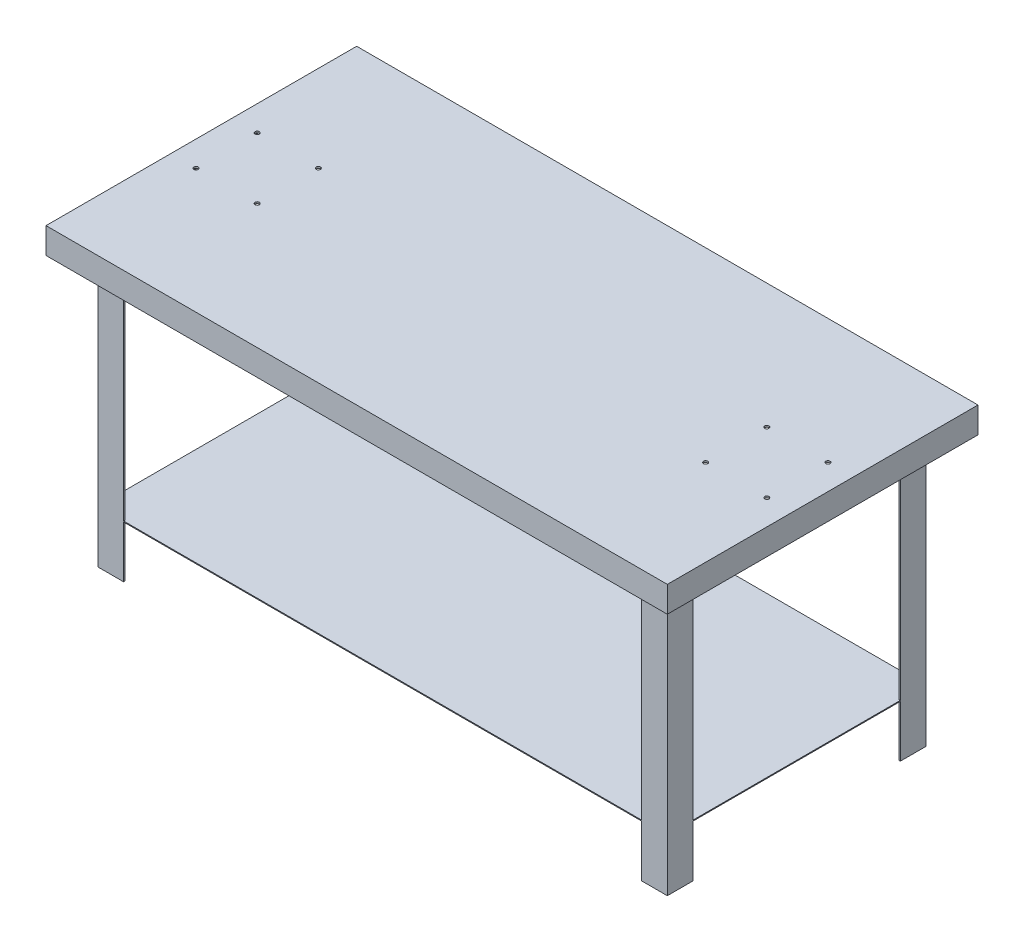
SolidWorks part; units mm, degrees
material "1023 Carbon Steel Sheet (SS)"
ref_plane "Front Plane" through (0, 0, 0) normal (0, 0, 1) x (1, 0, 0)
ref_plane "Top Plane" through (0, 0, 0) normal (0, 1, 0) x (1, 0, 0)
ref_plane "Right Plane" through (0, 0, 0) normal (1, 0, 0) x (0, 0, -1)
sketch "Sketch1" plane through (0, 0, 0) normal (1, 0, 0) x (0, 0, -1)
  line L0 (0, -1534.4769) -> (0, 75189.3682) construction
  line L1 (-457.2, 0) -> (457.2, 0)
  line L2 (457.2, 0) -> (457.2, -76.2)
  line L3 (457.2, -76.2) -> (381, -76.2)
  line L4 (-457.2, -76.2) -> (-381, -76.2)
  line L5 (-457.2, 0) -> (-457.2, -76.2)
  line L6 (-452.4375, -71.4375) -> (-381, -71.4375)
  line L7 (-452.4375, -4.7625) -> (-452.4375, -71.4375)
  line L8 (-452.4375, -4.7625) -> (452.4375, -4.7625)
  line L9 (452.4375, -4.7625) -> (452.4375, -71.4375)
  line L10 (452.4375, -71.4375) -> (381, -71.4375)
  line L11 (-381, -71.4375) -> (-381, -76.2)
  line L12 (381, -71.4375) -> (381, -76.2)
  point P10 (0, 0)
  dimension "D1" = 76.2
  dimension "D2" = 76.2
  dimension "D3" = 914.4
  dimension "D4" = 4.7625
extrude "Boss-Extrude1" add sketch "Sketch1" along normal mid plane 1828.8
sketch "Sketch2" plane through (0, 0, 0) normal (0, 0, 1) x (1, 0, 0)
  line L0 (0, -1000) -> (0, 49000) construction
  line L1 (-914.4, 0) -> (-914.4, -76.2)
  line L2 (-914.4, -76.2) -> (-838.2, -76.2)
  line L3 (914.4, -76.2) -> (-914.4, -76.2) construction
  line L4 (-838.2, -76.2) -> (-838.2, -71.4375)
  line L5 (-838.2, -71.4375) -> (-909.6375, -71.4375)
  line L6 (-909.6375, -71.4375) -> (-909.6375, 0)
  line L7 (914.4, 0) -> (-914.4, 0) construction
  line L8 (-909.6375, 0) -> (-914.4, 0)
  line L9 (909.6375, 0) -> (914.4, 0)
  line L10 (909.6375, -71.4375) -> (909.6375, 0)
  line L11 (838.2, -71.4375) -> (909.6375, -71.4375)
  line L12 (838.2, -76.2) -> (838.2, -71.4375)
  line L13 (914.4, -76.2) -> (838.2, -76.2)
  line L14 (914.4, 0) -> (914.4, -76.2)
  dimension "D1" = 4.7625
extrude "Boss-Extrude2" add sketch "Sketch2" along normal mid plane 914.4
sketch "Sketch3" plane through (0, 0, 0) normal (0, 1, 0) x (1, 0, 0)
  line L1 (-840, 90) -> (-660, 90)
  line L2 (-840, 90) -> (-840, -90)
  line L3 (-840, -90) -> (-660, -90)
  line L4 (-660, 90) -> (-660, -90)
  line L5 (-750, -90) -> (-750, 90) construction
  line L6 (-840, 0) -> (-660, 0) construction
  point P0 (-750, 0)
  dimension "D1" = 180
  dimension "D2" = 750
split line "Split Line1" [suppressed]
sketch "Sketch4" plane through (0, -4.7625, 0) normal (0, -1, 0) x (1, 0, 0)
  line L0 (0, -1000) -> (0, 49000) construction
  line L1 (-1000, 0) -> (49000, 0) construction
  line L2 (-762, 381) -> (-838.2, 381)
  line L3 (838.2, 381) -> (-838.2, 381) construction
  line L4 (-838.2, 381) -> (-838.2, 304.8)
  line L5 (-838.2, 381) -> (-838.2, -381) construction
  line L6 (-838.2, 304.8) -> (-833.646, 304.8)
  line L7 (-833.646, 304.8) -> (-833.646, 376.446)
  line L8 (-833.646, 376.446) -> (-762, 376.446)
  line L9 (-762, 376.446) -> (-762, 381)
  line L10 (-833.646, -376.446) -> (-762, -376.446)
  line L11 (-833.646, -304.8) -> (-833.646, -376.446)
  line L12 (-838.2, -304.8) -> (-833.646, -304.8)
  line L13 (-838.2, -381) -> (-838.2, -304.8)
  line L14 (-762, -381) -> (-838.2, -381)
  line L15 (-762, -376.446) -> (-762, -381)
  line L16 (833.646, -304.8) -> (833.646, -376.446)
  line L17 (838.2, -304.8) -> (833.646, -304.8)
  line L18 (838.2, -381) -> (838.2, -304.8)
  line L19 (762, -381) -> (838.2, -381)
  line L20 (762, -376.446) -> (762, -381)
  line L21 (833.646, -376.446) -> (762, -376.446)
  line L22 (833.646, 376.446) -> (762, 376.446)
  line L23 (833.646, 304.8) -> (833.646, 376.446)
  line L24 (838.2, 304.8) -> (833.646, 304.8)
  line L25 (838.2, 381) -> (838.2, 304.8)
  line L26 (762, 381) -> (838.2, 381)
  line L27 (762, 376.446) -> (762, 381)
  dimension "D1" = 4.554
  dimension "D2" = 76.2
extrude "Boss-Extrude3" add sketch "Sketch4" along normal offset from surface (865.1875 mm away) 869.95 up to face at (0, 0, 0)
sketch "Sketch5" plane through (0, -4.7625, 0) normal (0, -1, 0) x (1, 0, 0)
  line L1 (-838.2, 381) -> (838.2, 381)
  line L2 (-838.2, 381) -> (-838.2, -381)
  line L3 (-838.2, -381) -> (838.2, -381)
  line L4 (838.2, 381) -> (838.2, -381)
extrude "Boss-Extrude4" add sketch "Sketch5" against normal blind 2.657 from offset 712.7875
sketch "Sketch6" plane through (0, 0, 0) normal (0, 1, 0) x (1, 0, 0)
  line L0 (0, -1000) -> (0, 49000) construction
  line L3 (-840, -90) -> (-660, -90) construction
  line L4 (-840, -90) -> (-840, 90) construction
  line L5 (-840, 90) -> (-660, 90) construction
  line L6 (-660, -90) -> (-660, 90) construction
  line L7 (-750, 90) -> (-750, -90) construction
  line L8 (-840, 0) -> (-660, 0) construction
  circle A0 centre (-840, 90) radius 6.35
  circle A1 centre (-660, 90) radius 6.35
  circle A2 centre (-840, -90) radius 6.35
  circle A3 centre (-660, -90) radius 6.35
  circle A4 centre (660, -90) radius 6.35
  circle A5 centre (840, -90) radius 6.35
  circle A6 centre (840, 90) radius 6.35
  circle A7 centre (660, 90) radius 6.35
  point P4 (-750, 0)
  dimension "D3" = 12.7
  dimension "D1" = 180
  dimension "D2" = 750
extrude "Cut-Extrude1" cut sketch "Sketch6" against normal blind 10
